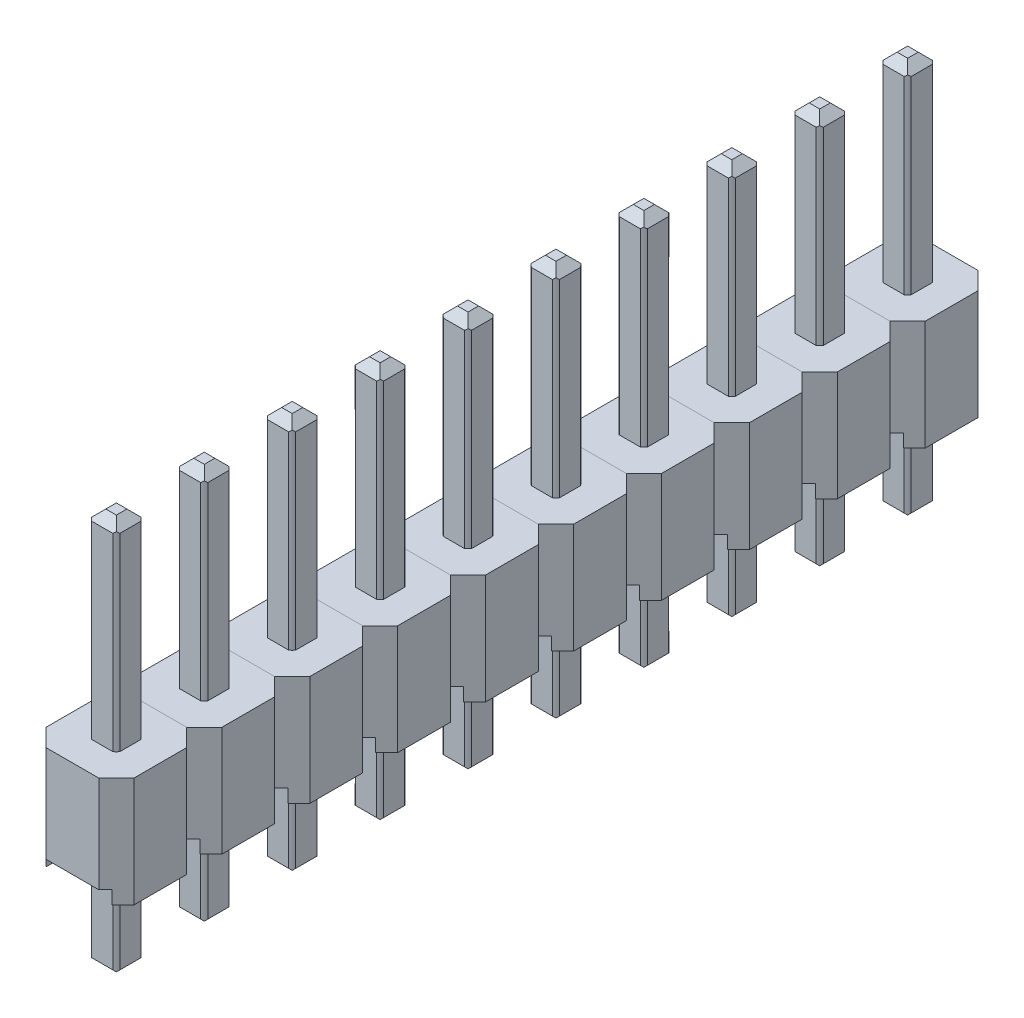
SolidWorks part; units mm, degrees
ref_plane "Front Plane" through (0, 0, 0) normal (0, 0, 1) x (1, 0, 0)
ref_plane "Top Plane" through (0, 0, 0) normal (0, 1, 0) x (1, 0, 0)
ref_plane "Right Plane" through (0, 0, 0) normal (1, 0, 0) x (0, 0, -1)
sketch "Sketch3" plane through (0, 0, 0) normal (0, 1, 0) x (1, 0, 0)
  line L1 (-1, -1) -> (1, -1)
  line L2 (-1, -1) -> (-1, 1)
  line L3 (-1, 1) -> (1, 1)
  line L4 (1, -1) -> (1, 1)
  line L5 (-1, -1) -> (1, 1) construction
  line L6 (-1, 1) -> (1, -1) construction
  point P0 (0, 0)
  dimension "D1" = 2
extrude "Boss-Extrude3" add sketch "Sketch3" along normal blind 2.5
sketch "Sketch4" plane through (0, 0, 1) normal (0, 0, 1) x (1, 0, 0)
  line L0 (-1, 0) -> (1, 0) construction
  line L1 (-0.75, 0) -> (0.75, 0)
  line L2 (-0.75, 0) -> (-0.75, 0.3)
  line L3 (-0.75, 0.3) -> (0.75, 0.3)
  line L4 (0.75, 0) -> (0.75, 0.3)
  line L5 (1, 2.5) -> (1, 0) construction
  line L6 (-1, 2.5) -> (-1, 0) construction
  dimension "D1" = 0.25
  dimension "D2" = 0.25
  dimension "D3" = 0.3
extrude "Cut-Extrude1" cut sketch "Sketch4" against normal through all
chamfer "Chamfer1" distance 0.4 angle 45 4 edges at (-1, 1.25, 1) (-1, 1.25, -1) (1, 1.25, -1) (1, 1.25, 1)
sketch "Sketch5" plane through (0, 0, 0) normal (0, 1, 0) x (1, 0, 0)
  line L1 (-0.24, -0.32) -> (0.24, -0.32)
  line L2 (-0.32, -0.24) -> (-0.32, 0.24)
  line L3 (-0.24, 0.32) -> (0.24, 0.32)
  line L4 (0.32, -0.24) -> (0.32, 0.24)
  line L5 (-0.2828, -0.2828) -> (0.2828, 0.2828) construction
  line L6 (-0.2828, 0.2828) -> (0.2828, -0.2828) construction
  arc A0 (0.32, 0.24) -> (0.24, 0.32) centre (0, 0) ccw
  arc A1 (-0.24, 0.32) -> (-0.32, 0.24) centre (0, 0) ccw
  arc A2 (-0.32, -0.24) -> (-0.24, -0.32) centre (0, 0) ccw
  arc A3 (0.24, -0.32) -> (0.32, -0.24) centre (0, 0) ccw
  dimension "D1" = 0.8
extrude "Boss-Extrude4" add sketch "Sketch5" along normal blind 7 and the other way blind 2
chamfer "Chamfer2" distance 0.2 angle 45 8 edges at (0.32, -2, 0) (0, -2, -0.32) (-0.32, -2, 0) (0, -2, 0.32) (0, 7, 0.32) (-0.32, 7, 0) (0, 7, -0.32) (0.32, 7, 0)
pattern_linear "LPattern1" count 10 spacing 2 along (0, 0, -1) of bodies 105
